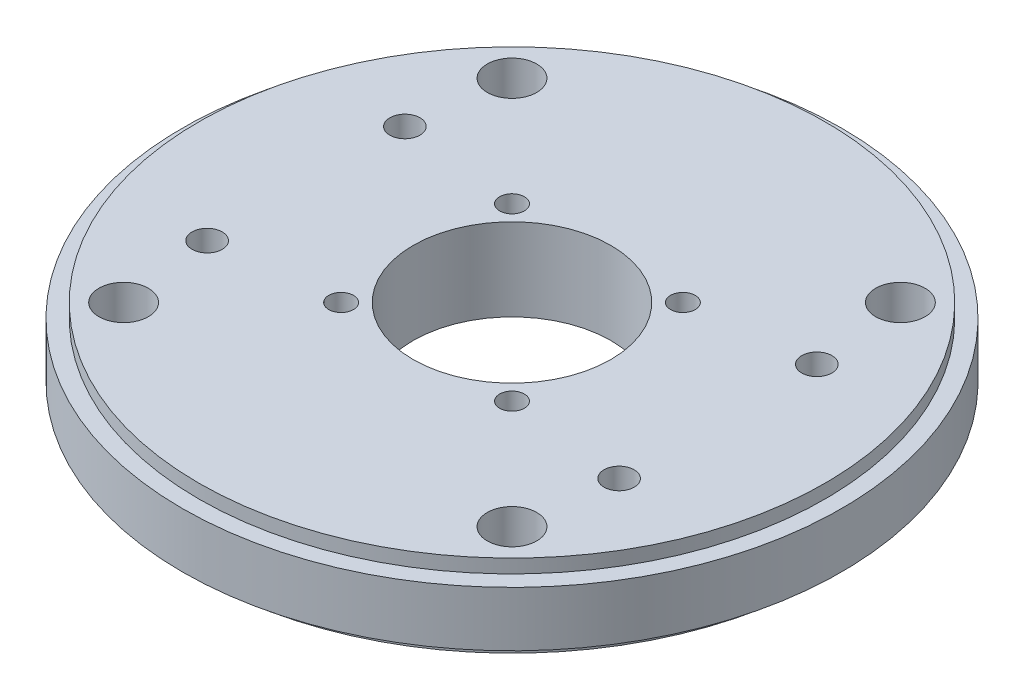
SolidWorks part; units mm, degrees
ref_plane "Front Plane" through (0, 0, 0) normal (0, 0, 1) x (1, 0, 0)
ref_plane "Top Plane" through (0, 0, 0) normal (0, 1, 0) x (1, 0, 0)
ref_plane "Right Plane" through (0, 0, 0) normal (1, 0, 0) x (0, 0, -1)
sketch "Sketch1" plane through (0, 0, 0) normal (0, 1, 0) x (1, 0, 0)
  circle A0 centre (0, 0) radius 57
  circle A1 centre (0, 0) radius 60
  dimension "D1" = 120
  dimension "D2" = 114
extrude "Extrude4" add sketch "Sketch1" along normal mid plane 15 contours A0
extrude "Extrude5" add sketch "Sketch" along normal mid plane 10
sketch "Sketch" plane through (0, 0, 0) normal (0, 1, 0) x (1, 0, 0) same geometry as "Sketch1"
sketch "Sketch5" plane through (0, 0, 0) normal (0, 1, 0) x (1, 0, 0)
  circle A0 centre (0, 0) radius 18
  dimension "D1" = 36
extrude "Extrude6" cut sketch "Sketch5" against normal through all both and the other way through all
hole_wizard "Ø4.5 (4.5) Diameter Hole1" positions "Sketch10" profile "Sketch11" hole size "Ø4.5" standard "ISO" end condition through all
sketch "Sketch10" plane through (0, -7.5, 0) normal (0, -1, 0) x (-1, 0, 0)
  point P6 (15.5563, 15.5563)
  point P9 (0, 0)
sketch "Sketch11" plane through (-15.5563, -7.5, -15.5563) normal (1, 0, 0) x (0, 0, -1)
  line L0 (0, 0) -> (0, 15)
  line L1 (0, 15) -> (2.25, 15)
  line L2 (2.25, 15) -> (2.25, 0)
  line L5 (2.25, 0) -> (0, 0)
  line L11 (0, -6.35) -> (0, 107.95) construction
  dimension "Thru Hole Dia." = 4.5
  dimension "Thru Hole Depth" = 15
ref_axis "Axis1" through (0, -8.25, 0) along (0, 1, 0)
pattern_circular "CirPattern1" count 4 over 360 about axis through (0, -8.25, 0) along (0, 1, 0) of "Ø4.5 (4.5) Diameter Hole1"
hole_wizard "M5 Clearance Hole1" positions "Sketch14" profile "Sketch15" hole size "M5" standard "ISO" end condition through all
sketch "Sketch14" plane through (0, 7.5, 0) normal (0, 1, 0) x (1, 0, 0)
  point P0 (-37.5, 18)
  point P3 (-37.5, -18)
  point P6 (37.5, -18)
  point P9 (37.5, 18)
sketch "Sketch15" plane through (-37.5, 7.5, -18) normal (1, 0, 0) x (0, 0, 1)
  line L0 (0, 0) -> (0, 15)
  line L1 (0, 15) -> (2.75, 15)
  line L2 (2.75, 15) -> (2.75, 0)
  line L5 (2.75, 0) -> (0, 0)
  line L11 (0, -6.35) -> (0, 107.95) construction
  dimension "Thru Hole Dia." = 5.5
  dimension "Thru Hole Depth" = 15
hole_wizard "M8 Clearance Hole2" positions "Sketch21" profile "Sketch22" hole size "M8" standard "ISO" end condition through all
sketch "Sketch21" plane through (0, 7.5, 0) normal (0, 1, 0) x (1, 0, 0)
  line L1 (-707.1068, -707.1068) -> (707.1068, 707.1068) construction
  line L2 (0, -8.25) -> (0, 8.25) construction
  circle A1 centre (15.5563, 15.5563) radius 2.25 construction
  point P0 (-35.3553, -35.3553)
  dimension "D1" = 45
  dimension "D2" = 50
sketch "Sketch22" plane through (-35.3553, 7.5, 35.3553) normal (1, 0, 0) x (0, 0, 1)
  line L0 (0, 0) -> (0, 15)
  line L1 (0, 15) -> (4.5, 15)
  line L2 (4.5, 15) -> (4.5, 0)
  line L5 (4.5, 0) -> (0, 0)
  line L11 (0, -6.35) -> (0, 107.95) construction
  dimension "Thru Hole Dia." = 9
  dimension "Thru Hole Depth" = 15
pattern_circular "CirPattern3" count 4 over 360 about axis through (0, -8.25, 0) along (0, 1, 0) of "M8 Clearance Hole2"
